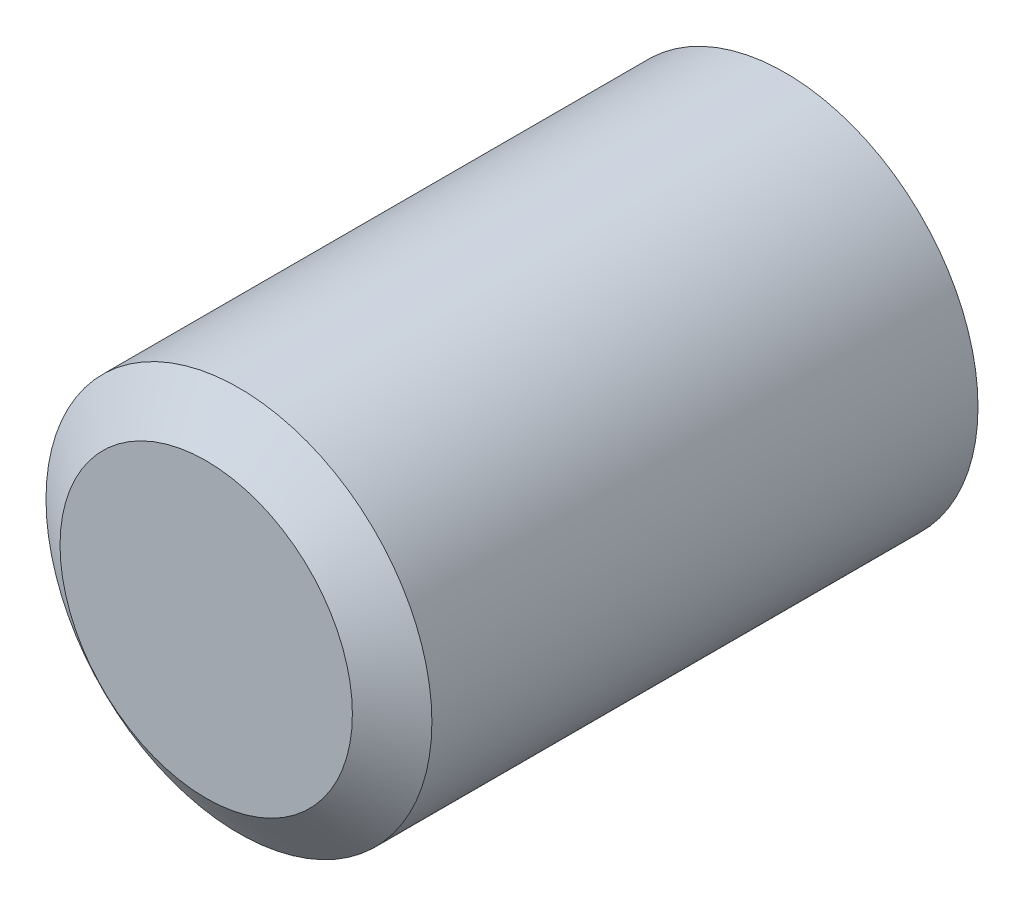
SolidWorks part; units mm, degrees
ref_plane "Front Plane" through (0, 0, 0) normal (0, 0, 1) x (1, 0, 0)
ref_plane "Top Plane" through (0, 0, 0) normal (0, 1, 0) x (1, 0, 0)
ref_plane "Right Plane" through (0, 0, 0) normal (1, 0, 0) x (0, 0, -1)
sketch "Sketch1" plane through (0, 0, 0) normal (0, 0, 1) x (1, 0, 0)
  circle A0 centre (0, 0) radius 3.175
  dimension "D1" = 6.35
extrude "Boss-Extrude1" add sketch "Sketch1" along normal blind 9.525
sketch "Sketch2" plane through (0, 0, 0) normal (1, 0, 0) x (0, 0, -1)
  line L0 (-9.525, 3.175) -> (-9.525, 2.4054)
  line L1 (-9.525, 3.175) -> (-9.525, -3.175) construction
  line L2 (-9.525, 2.4054) -> (-8.9862, 3.175)
  line L3 (0, 3.175) -> (-9.525, 3.175) construction
  line L4 (-8.9862, 3.175) -> (-9.525, 3.175)
  line L5 (0, 0) -> (-9.525, 0) construction
  dimension "D1" = 0.7696
  dimension "D2" = 55
revolve "Cut-Revolve1" cut sketch "Sketch2" angle 360 about L5
sketch "Sketch3" [suppressed] plane through (0, 0, 0) normal (0, 0, 1) x (1, 0, 0)
  circle A0 centre (0, 0) radius 4.7625
  dimension "D1" = 9.525
extrude "Boss-Extrude2" [suppressed] add sketch "Sketch3" against normal blind 6.35
sketch "Sketch4" [suppressed] plane through (0, 0, 0) normal (0, 0, 1) x (1, 0, 0)
  line L1 (0, -2.7496) -> (2.3812, -1.3748)
  line L2 (2.3812, -1.3748) -> (2.3813, 1.3748)
  line L3 (2.3813, 1.3748) -> (0, 2.7496)
  line L4 (0, 2.7496) -> (-2.3812, 1.3748)
  line L5 (-2.3812, 1.3748) -> (-2.3812, -1.3748)
  line L6 (-2.3812, -1.3748) -> (0, -2.7496)
  circle A0 centre (0, 0) radius 2.3813 construction
  dimension "D1" = 4.7625
extrude "Cut-Extrude1" [suppressed] cut sketch "Sketch4" along normal blind 3.5719 from surface
sketch "Sketch5" [suppressed] plane through (0, 0, -6.35) normal (0, 0, -1) x (-1, 0, 0)
  circle A0 centre (0, 0) radius 2.7496
extrude "Cut-Extrude2" [suppressed] cut sketch "Sketch5" against normal through all draft 45
chamfer "Chamfer1" [suppressed] distance 0.3962 angle 45
sketch "Sketch6" [suppressed] plane through (0, 0, 0) normal (1, 0, 0) x (0, 0, -1)
  line L0 (0, 3.175) -> (0, 6.7437)
  line L1 (0, 3.175) -> (-4.6018, 3.175)
  line L2 (0, 6.7437) -> (-0.2045, 6.7437)
  line L3 (-0.2045, 6.7437) -> (-4.0894, 3.3666)
  line L4 (0, 3.175) -> (-8.9862, 3.175) construction
  line L5 (0, 0) -> (-9.525, 0) construction
  line L6 (0, -3.175) -> (0, 3.175) construction
  line L7 (-9.525, 2.4054) -> (-9.525, -2.4054) construction
  arc A0 (-4.6018, 3.175) -> (-4.0894, 3.3666) centre (-4.6018, 3.956) ccw
  point P4 (0, 0)
  dimension "D1" = 6.7437
  dimension "D2" = 0.2045
  dimension "D3" = 4.0894
  dimension "D4" = 41
revolve "Revolve1" [suppressed] add sketch "Sketch6" angle 360 about L5
sketch "Sketch7" [suppressed] plane through (0, 0, 0) normal (0, 0, -1) x (-1, 0, 0)
  line L1 (-1.9844, -1.1457) -> (0, -2.2914)
  line L2 (0, -2.2914) -> (1.9844, -1.1457)
  line L3 (1.9844, -1.1457) -> (1.9844, 1.1457)
  line L4 (1.9844, 1.1457) -> (0, 2.2914)
  line L5 (0, 2.2914) -> (-1.9844, 1.1457)
  line L6 (-1.9844, 1.1457) -> (-1.9844, -1.1457)
  circle A0 centre (0, 0) radius 1.9844 construction
  dimension "D1" = 3.9688
extrude "Cut-Extrude3" [suppressed] cut sketch "Sketch7" against normal blind 2.8626
sketch "Sketch8" [suppressed] plane through (0, 0, 0) normal (0, 0, -1) x (-1, 0, 0)
  circle A0 centre (0, 0) radius 2.2914
extrude "Cut-Extrude4" [suppressed] cut sketch "Sketch8" against normal through all draft 45
sketch "Sketch10" [suppressed] plane through (0, 0, 0) normal (1, 0, 0) x (0, 0, -1)
  line L0 (0, 0) -> (0, 5.5499)
  line L1 (0, 5.5499) -> (0.4536, 5.5499)
  line L2 (0, 0) -> (0.866, 0)
  line L3 (0.866, 0) -> (2.0117, 1.9844)
  line L4 (2.0117, 1.9844) -> (3.3528, 1.9844)
  line L5 (3.3528, 1.9844) -> (3.3528, 2.7781)
  line L6 (0, 0) -> (-4.1183, 0) construction
  arc A1 (0.4536, 5.5499) -> (3.3528, 2.7781) centre (-2.0778, 0) cw
  dimension "D1" = 0.4536
  dimension "D2" = 5.5499
  dimension "D3" = 0.866
  dimension "D4" = 120
  dimension "D5" = 1.9844
  dimension "D6" = 2.7781
  dimension "D7" = 1.3411
revolve "Revolve2" [suppressed] add sketch "Sketch10" angle 360 about L6
sketch "Sketch11" [suppressed] plane through (0, 0, -3.3528) normal (0, 0, -1) x (-1, 0, 0)
  line L1 (-1.9844, -1.1457) -> (0, -2.2914)
  line L2 (0, -2.2914) -> (1.9844, -1.1457)
  line L3 (1.9844, -1.1457) -> (1.9844, 1.1457)
  line L4 (1.9844, 1.1457) -> (0, 2.2914)
  line L5 (0, 2.2914) -> (-1.9844, 1.1457)
  line L6 (-1.9844, 1.1457) -> (-1.9844, -1.1457)
  circle A0 centre (0, 0) radius 1.9844 construction
extrude "Cut-Extrude5" [suppressed] cut sketch "Sketch11" against normal up to vertex
sketch "Sketch12" [suppressed] plane through (0, 0, -3.3528) normal (0, 0, -1) x (-1, 0, 0)
  circle A0 centre (0, 0) radius 2.2914
extrude "Cut-Extrude6" [suppressed] cut sketch "Sketch12" against normal through all draft 45
sketch "Sketch13" [suppressed] plane through (0, 0, 0) normal (1, 0, 0) x (0, 0, -1)
  line L0 (0, 0) -> (0, 4.7625)
  line L1 (0, -3.175) -> (0, 3.175) construction
  line L2 (0, 4.7625) -> (2.54, 4.7625)
  line L3 (2.54, 4.7625) -> (3.175, 4.1275)
  line L4 (3.175, 4.1275) -> (3.175, 0)
  line L5 (3.175, 0) -> (0, 0)
  line L6 (0, 0) -> (-6.666, 0) construction
  dimension "D1" = 3.175
  dimension "D2" = 4.7625
  dimension "D3" = 4.1275
  dimension "D4" = 2.54
revolve "Revolve3" [suppressed] add sketch "Sketch13" angle 360 about L6
sketch "Sketch14" [suppressed] plane through (0, 0, -3.175) normal (0, 0, -1) x (-1, 0, 0)
  line L1 (0, -1.8331) -> (1.5875, -0.9165)
  line L2 (1.5875, -0.9165) -> (1.5875, 0.9165)
  line L3 (1.5875, 0.9165) -> (0, 1.8331)
  line L4 (0, 1.8331) -> (-1.5875, 0.9165)
  line L5 (-1.5875, 0.9165) -> (-1.5875, -0.9165)
  line L6 (-1.5875, -0.9165) -> (0, -1.8331)
  circle A0 centre (0, 0) radius 1.5875 construction
  dimension "D1" = 3.175
extrude "Cut-Extrude7" [suppressed] cut sketch "Sketch14" against normal blind 2.3876
sketch "Sketch15" [suppressed] plane through (0, 0, -3.175) normal (0, 0, -1) x (-1, 0, 0)
  circle A0 centre (0, 0) radius 1.8331
extrude "Cut-Extrude8" [suppressed] cut sketch "Sketch15" against normal through all draft 45
equation "\"Length\"= .375"
equation "\"D1@Boss-Extrude1\"=\"Length\""
